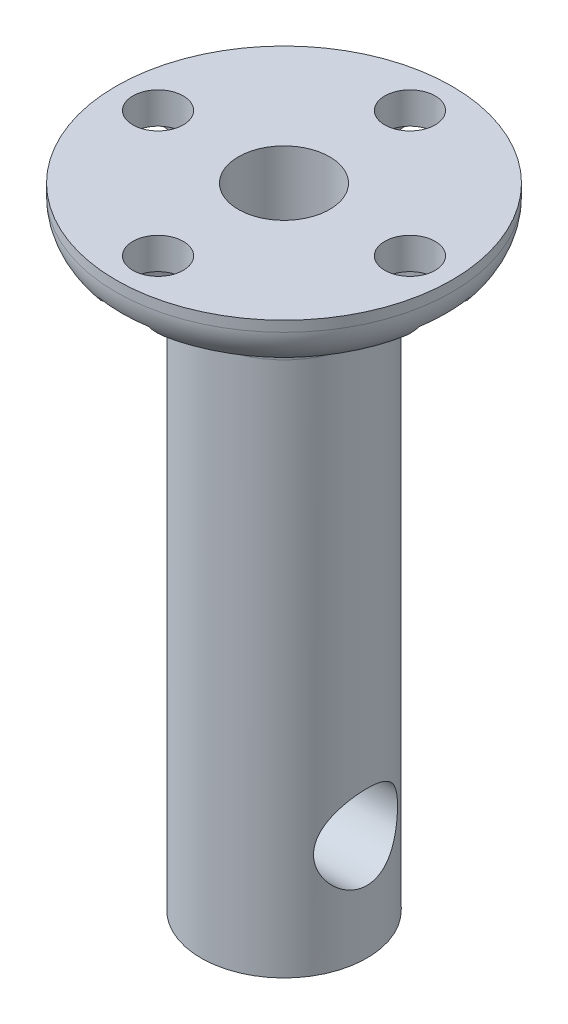
SolidWorks part; units mm, degrees
ref_plane "Front Plane" through (0, 0, 0) normal (0, 0, 1) x (1, 0, 0)
ref_plane "Top Plane" through (0, 0, 0) normal (0, 1, 0) x (1, 0, 0)
ref_plane "Right Plane" through (0, 0, 0) normal (1, 0, 0) x (0, 0, -1)
sketch "Sketch1" plane through (0, 0, 0) normal (0, 0, 1) x (1, 0, 0)
  line L0 (0, 0) -> (-7.9, 0)
  line L1 (-7.9, 0) -> (-7.9, 55)
  line L5 (0, 40) -> (0, 0)
  line L7 (-4.35, 60) -> (-4.35, 40)
  line L8 (-4.35, 40) -> (0, 40)
  line L14 (-16, 60) -> (-4.35, 60)
  line L15 (-7.9, 55) -> (-16, 55)
  line L16 (-16, 55) -> (-16, 60)
  point P11 (-16, 60)
  point P14 (-7.9, 55)
  dimension "D1" = 7.9
  dimension "D2" = 4.35
  dimension "D3" = 55
  dimension "D4" = 5
  dimension "D5" = 20
  dimension "D6" = 16
revolve "Revolve1" add sketch "Sketch1" angle 360 about L5
sketch "Sketch3" plane through (0, 0, 0) normal (1, 0, 0) x (0, 0, -1)
  line L0 (-7.9, 10) -> (7.9, 10) construction
  line L1 (-7.9, 55) -> (-7.9, 0) construction
  line L4 (-7.9, 0) -> (7.9, 0) construction
  line L5 (7.9, 0) -> (7.9, 55) construction
  circle A1 centre (0, 10) radius 4
  dimension "D1" = 10
  dimension "D2" = 8
extrude "Cut-Extrude1" cut sketch "Sketch3" against normal through all both and the other way through all contours A1
sketch "Sketch4" plane through (0, 60, 0) normal (0, 1, 0) x (1, 0, 0)
  line L0 (0, 0) -> (-12, 0) construction
  line L1 (0, 0) -> (-12, 0) construction
  circle A0 centre (-12, 0) radius 2 construction
  circle A1 centre (0, 12) radius 2 construction
  circle A2 centre (12, 0) radius 2 construction
  circle A3 centre (0, -12) radius 2 construction
  point P4 (7.45, 10.26)
  point P5 (0, 0)
  dimension "D2" = 4
  dimension "D1" = 12
  dimension "D3" = 4
sketch "Sketch5" plane through (0, 55, 0) normal (0, -1, 0) x (1, 0, 0)
  line L0 (2.1362, 15.7) -> (-2.1362, 15.7)
  line L1 (-15.7, 2.1362) -> (-15.7, -2.1362)
  line L2 (-15.7, -2.1362) -> (-12, -4.2724)
  line L3 (-12, -4.2724) -> (-8.3, -2.1362)
  line L4 (-8.3, -2.1362) -> (-8.3, 2.1362)
  line L5 (-8.3, 2.1362) -> (-12, 4.2724)
  line L6 (-12, 4.2724) -> (-15.7, 2.1362)
  line L7 (-2.1362, 15.7) -> (-4.2724, 12)
  line L8 (-4.2724, 12) -> (-2.1362, 8.3)
  line L9 (-2.1362, 8.3) -> (2.1362, 8.3)
  line L10 (2.1362, 8.3) -> (4.2724, 12)
  line L11 (4.2724, 12) -> (2.1362, 15.7)
  line L12 (15.7, -2.1362) -> (15.7, 2.1362)
  line L13 (15.7, 2.1362) -> (12, 4.2724)
  line L14 (12, 4.2724) -> (8.3, 2.1362)
  line L15 (8.3, 2.1362) -> (8.3, -2.1362)
  line L16 (8.3, -2.1362) -> (12, -4.2724)
  line L17 (12, -4.2724) -> (15.7, -2.1362)
  line L18 (-2.1362, -15.7) -> (2.1362, -15.7)
  line L19 (2.1362, -15.7) -> (4.2724, -12)
  line L20 (4.2724, -12) -> (2.1362, -8.3)
  line L21 (2.1362, -8.3) -> (-2.1362, -8.3)
  line L22 (-2.1362, -8.3) -> (-4.2724, -12)
  line L23 (-4.2724, -12) -> (-2.1362, -15.7)
  circle A0 centre (-12, 0) radius 3.7 construction
  point P1 (0, 0)
  point P30 (0, 0)
  dimension "D1" = 7.4
  dimension "D2" = 4
hole_wizard "M4 Clearance Hole1" positions "Sketch6" profile "Sketch7" hole size "M4" standard "ANSI Metric" end condition through all
sketch "Sketch6" plane through (0, 60, 0) normal (0, 1, 0) x (1, 0, 0)
  point P0 (0, 12)
  point P3 (-12, 0)
  point P6 (12, 0)
  point P9 (0, -12)
sketch "Sketch7" plane through (0, 60, -12) normal (1, 0, 0) x (0, 0, 1)
  line L0 (0, 0) -> (0, 60)
  line L1 (0, 60) -> (2.4, 60)
  line L2 (2.4, 60) -> (2.4, 0)
  line L5 (2.4, 0) -> (0, 0)
  line L11 (0, -6.35) -> (0, 107.95) construction
  dimension "Thru Hole Dia." = 4.8
  dimension "Thru Hole Depth" = 60
extrude "Cut-Extrude3" cut sketch "Sketch5" against normal blind 2 and the other way through all
fillet "Fillet1" radius 4 1 edges at (-16, 55, 0)
fillet "Fillet2" radius 4 1 edges at (-7.9, 55, 0)
